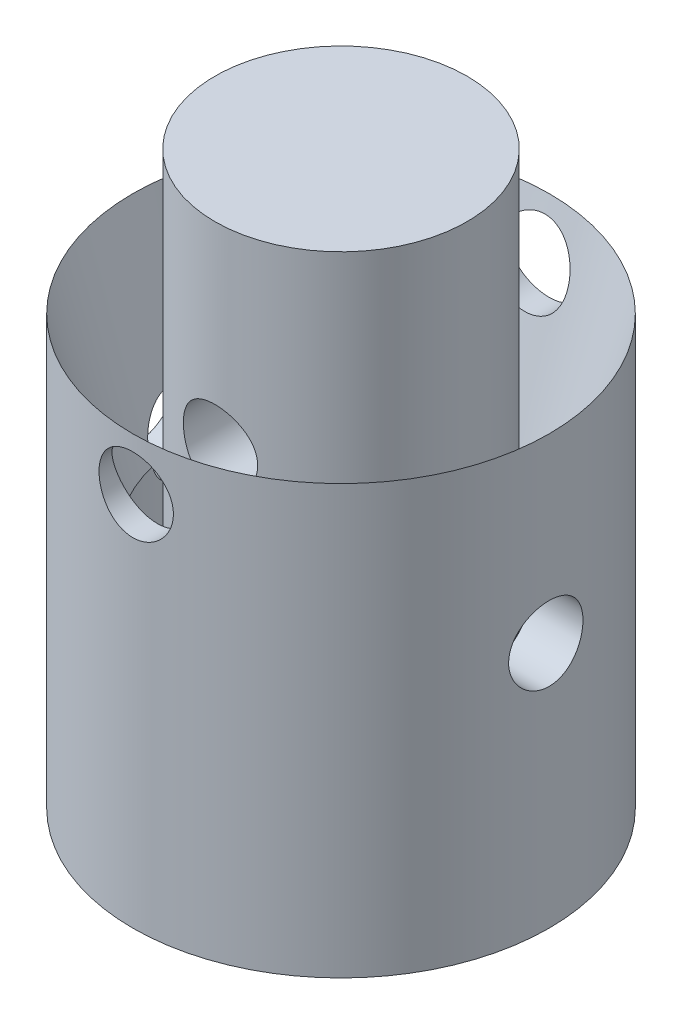
SolidWorks part; units mm, degrees
ref_plane "Front Plane" through (0, 0, 0) normal (1, 0, 0) x (0, 1, 0)
ref_plane "Top Plane" through (0, 0, 0) normal (0, 0, 1) x (0, 1, 0)
ref_plane "Right Plane" through (0, 0, 0) normal (0, 1, 0) x (-1, 0, 0)
sketch "Sketch1" plane through (0, 0, 0) normal (1, 0, 0) x (0, 1, 0)
  line L0 (0, 0) -> (60.96, 0)
  line L1 (60.96, 0) -> (60.96, 13.462)
  line L2 (60.96, 13.462) -> (12.7, 13.462)
  line L3 (12.7, 13.462) -> (12.7, 16.7005)
  line L4 (12.7, 16.7005) -> (25.4, 16.7005)
  line L5 (25.4, 16.7005) -> (45.72, 22.225)
  line L6 (45.72, 22.225) -> (0, 22.225)
  line L7 (0, 22.225) -> (0, 0)
  dimension "D1" = 48.26
  dimension "D2" = 13.462
  dimension "D3" = 12.7
  dimension "D4" = 12.7
  dimension "D5" = 16.7005
  dimension "D6" = 33.02
  dimension "D7" = 22.225
revolve "Revolve1" add sketch "Sketch1" angle 360 about L0
sketch "Sketch2" plane through (0, 0, 0) normal (0, 0, 1) x (0, 1, 0)
  line L0 (45.72, -22.225) -> (45.72, 22.225) construction
  line L1 (0, 0) -> (45.72, 0) construction
  line L2 (45.72, 0) -> (53.848, 0) construction
  line L3 (53.848, 0) -> (40.0897, 0) construction
  line L4 (40.0897, 0) -> (26.3313, 0) construction
  line L5 (26.3313, 0) -> (12.573, 0) construction
  circle A1 centre (40.0897, 0) radius 3.9687
  point P0 (45.72, 0)
  point P1 (-3.4062, 6.1377)
  point P4 (0, 0)
  point P8 (40.0897, 0)
  point P9 (26.3313, 0)
  dimension "D3" = 7.9375
  dimension "D1" = 8.128
  dimension "D2" = 41.275
extrude "Cut-Extrude1" cut sketch "Sketch2" against normal through all both and the other way through all contours A1
sketch "Sketch4" plane through (0, 0, 0) normal (1, 0, 0) x (0, 1, 0)
  circle A0 centre (26.3313, 0) radius 3.9688
  point P0 (26.3313, 0)
  dimension "D1" = 7.9375
extrude "Cut-Extrude2" cut sketch "Sketch4" against normal through all both and the other way through all
